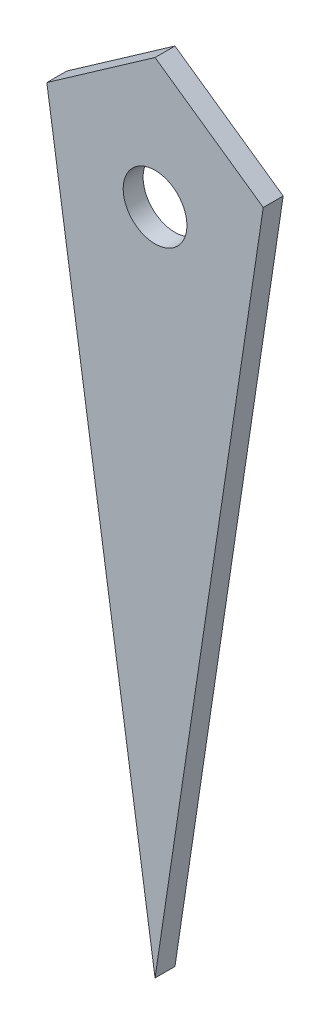
SolidWorks part; units mm, degrees
material "1.0050 (E295)"
ref_plane "Plan de face" through (0, 0, 0) normal (0, 0, 1) x (1, 0, 0)
ref_plane "Plan de dessus" through (0, 0, 0) normal (0, 1, 0) x (1, 0, 0)
ref_plane "Plan de droite" through (0, 0, 0) normal (1, 0, 0) x (0, 0, -1)
sketch "Esquisse1" plane through (0, 0, 0) normal (0, 0, 1) x (1, 0, 0)
  line L0 (0, 0) -> (-60, 400)
  line L1 (-60, 400) -> (60, 400)
  line L2 (60, 400) -> (0, 0)
  dimension "D1" = 400
  dimension "D2" = 120
  dimension "D3" = 60
base flange "Tôle de base pliée1" sketch "Esquisse1" thickness 10 reverse thickness direction no parameters "D1"=5
sketch "Esquisse6" plane through (0, 0, -10) normal (0, 0, -1) x (-1, 0, 0)
  line L0 (0, 400) -> (54.2971, 361.9808)
  line L1 (-60, 400) -> (60, 400) construction
  line L2 (60, 400) -> (0, 0) construction
  line L3 (0, 400) -> (-54.2971, 361.9808)
  line L4 (0, 0) -> (-60, 400) construction
  line L5 (54.2971, 361.9808) -> (60, 400)
  line L6 (60, 400) -> (0, 400)
  line L7 (0, 400) -> (-60, 400)
  line L8 (-60, 400) -> (-54.2971, 361.9808)
  dimension "D1" = 110
extrude "Enlèv. mat.-Extru.1" cut sketch "Esquisse6" against normal through all
sketch "Esquisse7" plane through (0, 0, -10) normal (0, 0, -1) x (-1, 0, 0)
  circle A0 centre (0, 335) radius 16
  dimension "D1" = 32
  dimension "D3" = 65
extrude "Enlèv. mat.-Extru.2" cut sketch "Esquisse7" against normal blind 10 normal cut yes
sketch "Lignes de pliage1" [suppressed] plane through (0, 0, 0) normal (0, 1, 0) x (1, 0, 0)
sketch "Cube de visualisation1" [suppressed] plane through (0, 0, 0) normal (0, 1, 0) x (1, 0, 0)
sheet metal parameters "Tôlerie1" thickness 10 parameters "D1"=5
flat pattern "Etat déplié1" [suppressed]
sketch "Lignes de pliage2" plane through (0, 0, 0) normal (0, 1, 0) x (1, 0, 0)
sketch3d "Cube de visualisation2" [suppressed]
  line L0 (-60, 500, 0) -> (-60, 0, 0) construction
  line L1 (60, 500, 0) -> (60, 0, 0) construction
  line L2 (-60, 500, 0) -> (60, 500, 0) construction
  line L3 (-60, 0, 0) -> (60, 0, 0) construction
sheet metal parameters "Tôlerie2" thickness 10 parameters "D1"=5
flat pattern "Etat déplié1"
sketch "Lignes de pliage2" plane through (0, 0, 0) normal (0, 1, 0) x (1, 0, 0)
sketch3d "Cube de visualisation2" [suppressed]
  line L0 (46.4736, 505.5768, 0) -> (105.6219, 12.6746, 0) construction
  line L1 (-59.1483, 492.9022, 0) -> (0, 0, 0) construction
  line L2 (46.4736, 505.5768, 0) -> (-59.1483, 492.9022, 0) construction
  line L3 (105.6219, 12.6746, 0) -> (0, 0, 0) construction
sheet metal parameters "Tôlerie3" thickness 10 parameters "D1"=5
flat pattern "Etat déplié1"
sketch "Lignes de pliage2" plane through (0, 0, 0) normal (0, 1, 0) x (1, 0, 0)
sketch3d "Cube de visualisation2" [suppressed]
  line L0 (47.5249, 407.1287, 0) -> (106.2046, 15.9307, 0) construction
  line L1 (-58.6797, 391.198, 0) -> (0, 0, 0) construction
  line L2 (47.5249, 407.1287, 0) -> (-58.6797, 391.198, 0) construction
  line L3 (106.2046, 15.9307, 0) -> (0, 0, 0) construction
